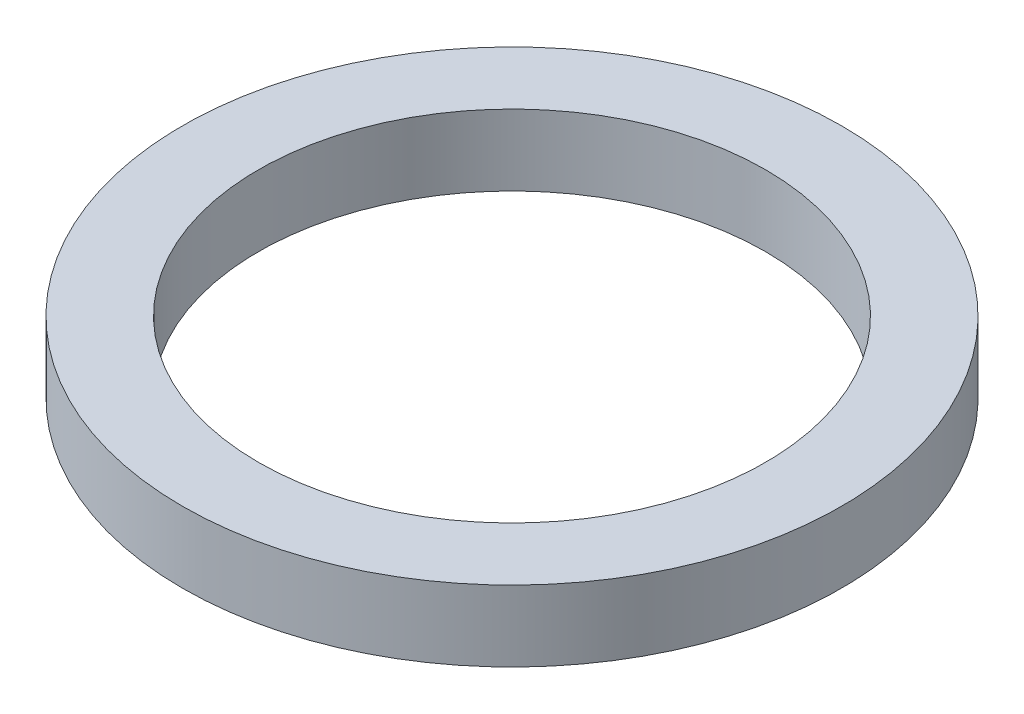
SolidWorks part; units mm, degrees
ref_plane "Front Plane" through (0, 0, 0) normal (0, 0, 1) x (1, 0, 0)
ref_plane "Top Plane" through (0, 0, 0) normal (0, 1, 0) x (1, 0, 0)
ref_plane "Right Plane" through (0, 0, 0) normal (1, 0, 0) x (0, 0, -1)
sketch "Sketch1" plane through (0, 0, 0) normal (0, 1, 0) x (1, 0, 0)
  circle A0 centre (0, 0) radius 2.5
  circle A1 centre (0, 0) radius 5
  dimension "D1" = 10
  dimension "D2" = 5
extrude "Boss-Extrude1" [suppressed] add sketch "Sketch1" along normal blind 4
sketch "Sketch2" [suppressed] plane through (0, 0, 0) normal (0, 1, 0) x (1, 0, 0)
  circle A0 centre (0, 0) radius 7.5
  circle A1 centre (0, 0) radius 14
  dimension "D1" = 15
  dimension "D2" = 28
extrude "Boss-Extrude2" [suppressed] add sketch "Sketch2" along normal blind 8
sketch "Sketch3" plane through (0, 0, 0) normal (0, 1, 0) x (1, 0, 0)
  circle A0 centre (0, 0) radius 25
  circle A1 centre (0, 0) radius 32.5
  dimension "D1" = 65
  dimension "D2" = 50
extrude "Boss-Extrude3" add sketch "Sketch3" along normal blind 7
